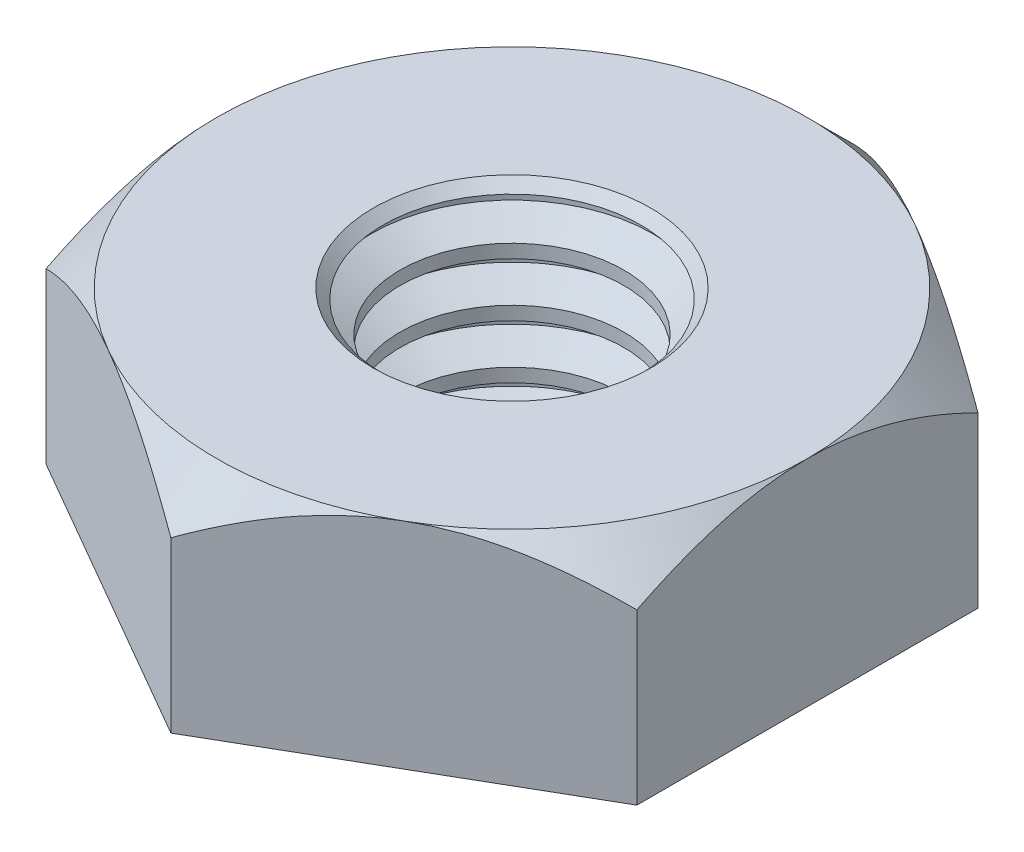
SolidWorks part; units mm, degrees
ref_plane "Front" through (0, 0, 0) normal (0, 0, 1) x (1, 0, 0)
ref_plane "Top" through (0, 0, 0) normal (0, 1, 0) x (1, 0, 0)
ref_plane "Right" through (0, 0, 0) normal (1, 0, 0) x (0, 0, -1)
sketch "Sketch1" plane through (0, 0, 0) normal (0, 1, 0) x (1, 0, 0)
  line L1 (0, 5.041) -> (-4.3656, 2.5205)
  line L2 (-4.3656, 2.5205) -> (-4.3656, -2.5205)
  line L3 (-4.3656, -2.5205) -> (0, -5.041)
  line L4 (0, -5.041) -> (4.3656, -2.5205)
  line L5 (4.3656, -2.5205) -> (4.3656, 2.5205)
  line L6 (4.3656, 2.5205) -> (0, 5.041)
  circle A0 centre (0, 0) radius 4.3656 construction
  dimension "Hex Flats" = 8.7312
extrude "Extrude1" add sketch "Sketch1" along normal blind 3.175
sketch "Sketch3" plane through (0, 0, 0) normal (1, 0, 0) x (0, 0, -1)
  line L0 (4.3656, 3.175) -> (5.041, 2.4996)
  line L1 (2.5205, 3.175) -> (5.041, 3.175) construction
  line L2 (5.041, 3.175) -> (5.041, 0) construction
  line L3 (5.041, 2.4996) -> (5.041, 3.175)
  line L4 (5.041, 3.175) -> (4.3656, 3.175)
  line L5 (0, 0.542) -> (0, -0.542) construction
  dimension "D1" = 45
  dimension "D2" = 8.7312
revolve "Cut-Revolve2" cut sketch "Sketch3" angle 360 about L5
sketch "Sketch2" plane through (0, 0, 0) normal (0, 0, 1) x (1, 0, 0)
  line L0 (0, 1.6636) -> (0, -0.3796) construction
  line L1 (0, 3.175) -> (1.6532, 3.175)
  line L3 (0, 3.175) -> (4.3656, 3.175) construction
  line L4 (0, 2.3813) -> (1.6532, 2.3812)
  line L5 (1.6532, 3.175) -> (2.0828, 2.927)
  line L6 (2.0828, 2.927) -> (2.0828, 2.8277)
  line L7 (2.0828, 2.8277) -> (1.6532, 2.5797)
  line L9 (1.6532, 2.3812) -> (1.6532, 2.5797)
  line L10 (0, 2.3813) -> (0, 3.175)
  line L11 (1.6532, 3.175) -> (1.6532, 2.5797) construction
  line L12 (2.0828, 2.8773) -> (1.6532, 2.8773) construction
  dimension "D1" = 60
  dimension "D2" = 0.1984
  dimension "D5" = 0.0992
  dimension "Pitch" = 0.7937
  dimension "Major Dia." = 4.1656
revolve "Cut-Revolve1" cut sketch "Sketch2" angle 360 about L0
pattern_linear "LPattern2" count 5 spacing 0.7937 along (0, -1, 0) of "Cut-Revolve1"
chamfer "Chamfer1" distance 0.3969 angle 45 1 edges at (0, 3.175, 1.6532) first distance on face at (0, 3.175, 0)
equation "\"D5@Sketch2\"=\"Pitch@Sketch2\"/8"
equation "\"D2@Sketch2\"=\"Pitch@Sketch2\"/4"
equation "\"D3@LPattern2\"=\"Pitch@Sketch2\""
equation "\"D1@LPattern2\"=int(\"Height@Extrude1\"/\"Pitch@Sketch2\")+1"
equation "\"D2@Sketch3\"=\"Hex Flats@Sketch1\""
equation "\"D1@Chamfer1\"=\"Pitch@Sketch2\"/2"
